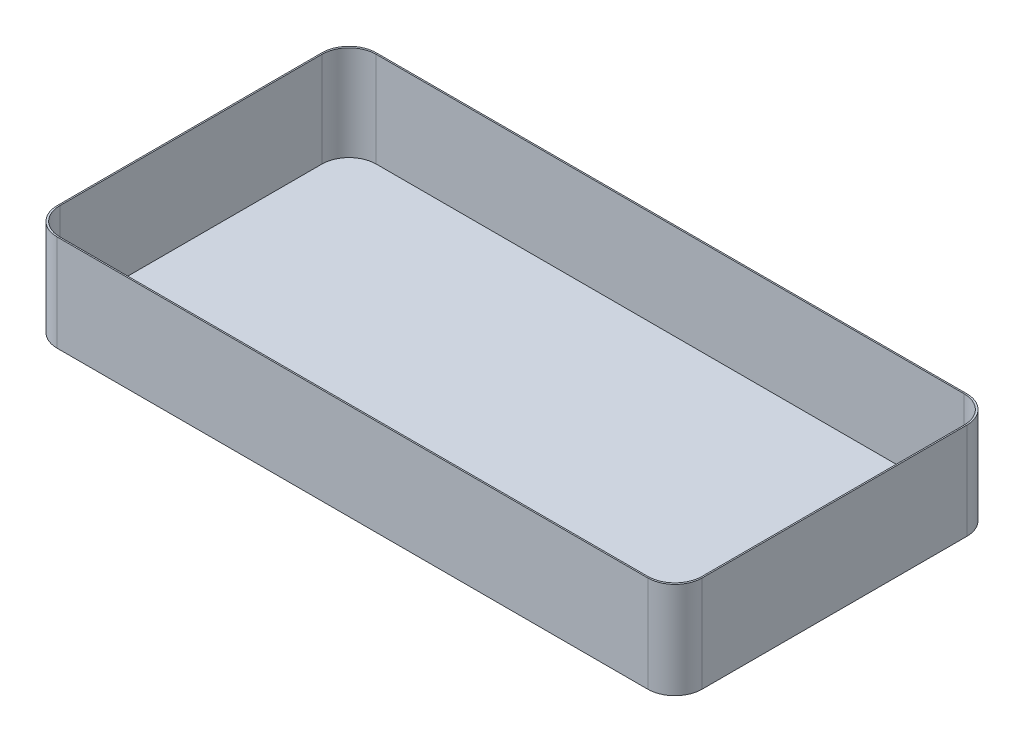
SolidWorks part; units mm, degrees
ref_plane "Front Plane" through (0, 0, 0) normal (0, 0, 1) x (1, 0, 0)
ref_plane "Top Plane" through (0, 0, 0) normal (0, 1, 0) x (1, 0, 0)
ref_plane "Right Plane" through (0, 0, 0) normal (1, 0, 0) x (0, 0, -1)
sketch "Sketch1" plane through (0, 0, 0) normal (0, 1, 0) x (1, 0, 0)
  line L1 (-603.25, -298.45) -> (603.25, -298.45)
  line L2 (-603.25, -298.45) -> (-603.25, 298.45)
  line L3 (-603.25, 298.45) -> (603.25, 298.45)
  line L4 (603.25, -298.45) -> (603.25, 298.45)
  line L5 (-603.25, -298.45) -> (603.25, 298.45) construction
  line L6 (-603.25, 298.45) -> (603.25, -298.45) construction
  line L7 (-600.71, -295.91) -> (600.71, -295.91)
  line L8 (-600.71, -295.91) -> (-600.71, 295.91)
  line L9 (-600.71, 295.91) -> (600.71, 295.91)
  line L10 (600.71, -295.91) -> (600.71, 295.91)
  line L11 (-600.71, -295.91) -> (600.71, 295.91) construction
  line L12 (-600.71, 295.91) -> (600.71, -295.91) construction
  point P0 (0, 0)
  point P6 (0, 0)
  dimension "D1" = 596.9
  dimension "D2" = 1206.5
  dimension "D3" = 2.54
  dimension "D4" = 2.54
extrude "Boss-Extrude1" add sketch "Sketch1" along normal blind 177.8
sketch "Sketch2" plane through (0, 0, 0) normal (0, -1, 0) x (1, 0, 0)
  line L1 (603.25, 298.45) -> (-603.25, 298.45)
  line L2 (603.25, 298.45) -> (603.25, -298.45)
  line L3 (603.25, -298.45) -> (-603.25, -298.45)
  line L4 (-603.25, 298.45) -> (-603.25, -298.45)
  line L5 (603.25, 298.45) -> (-603.25, -298.45) construction
  line L6 (603.25, -298.45) -> (-603.25, 298.45) construction
  point P0 (0, 0)
extrude "Boss-Extrude2" add sketch "Sketch2" along normal blind 2.54
fillet "Fillet1" radius 50.8 8 edges at (600.71, 88.9, 295.91) (-600.71, 88.9, 295.91) (-600.71, 88.9, -295.91) (600.71, 88.9, -295.91) (603.25, 87.63, -298.45) (603.25, 87.63, 298.45) (-603.25, 87.63, 298.45) (-603.25, 87.63, -298.45)
